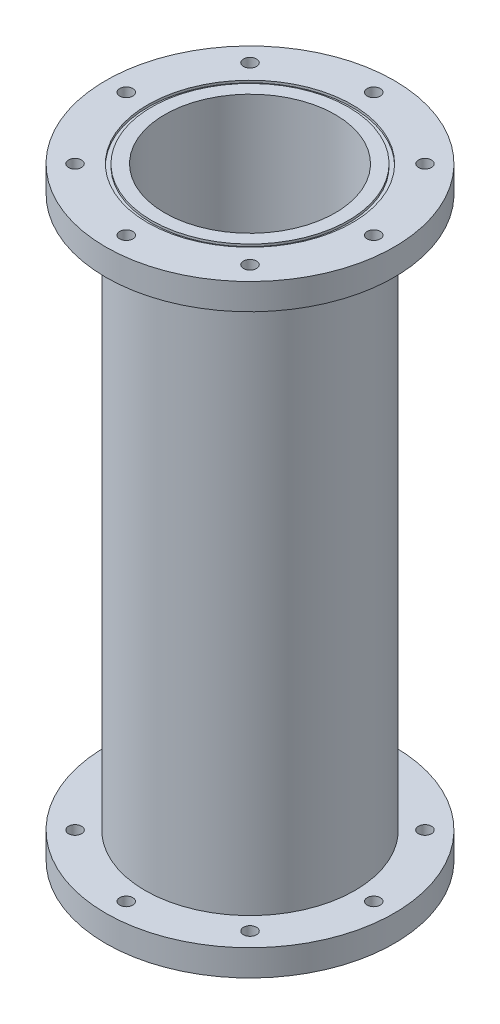
SolidWorks part; units mm, degrees
ref_plane "Front Plane" through (0, 0, 0) normal (0, 0, 1) x (1, 0, 0)
ref_plane "Top Plane" through (0, 0, 0) normal (0, 1, 0) x (1, 0, 0)
ref_plane "Right Plane" through (0, 0, 0) normal (1, 0, 0) x (0, 0, -1)
sketch "Sketch2" plane through (0, 0, 0) normal (0, 1, 0) x (1, 0, 0)
  circle A0 centre (0, 0) radius 41.275
  circle A1 centre (0, 0) radius 50.8
  dimension "D1" = 101.6
  dimension "D2" = 82.55
extrude "Base Cylinder" add sketch "Sketch2" along normal blind 292.1
sketch "Sketch3" plane through (0, 0, 0) normal (0, -1, 0) x (1, 0, 0)
  circle A0 centre (0, 0) radius 41.275
  circle A1 centre (0, 0) radius 69.85
  dimension "D1" = 139.7
extrude "Aft Flange" add sketch "Sketch3" against normal blind 12.7
sketch "Sketch4" plane through (0, 292.1, 0) normal (0, 1, 0) x (1, 0, 0)
  circle A0 centre (0, 0) radius 41.275
  circle A1 centre (0, 0) radius 69.85
extrude "Forward Flange" add sketch "Sketch4" against normal blind 12.7
sketch "Sketch6" plane through (0, 0, 0) normal (0, -1, 0) x (1, 0, 0)
  circle A0 centre (0, 0) radius 49.4792
  circle A1 centre (0, 0) radius 47.625
  dimension "D1" = 98.9584
  dimension "D2" = 95.25
extrude "O-Ring Slot 1" cut sketch "Sketch6" against normal blind 1.1176
sketch "Sketch7" plane through (0, 292.1, 0) normal (0, 1, 0) x (1, 0, 0)
  circle A0 centre (0, 0) radius 49.53
  circle A1 centre (0, 0) radius 47.625
  dimension "D1" = 99.06
  dimension "D2" = 95.25
extrude "O-Ring Slot 2" cut sketch "Sketch7" against normal blind 1.1176
sketch "Sketch8" plane through (0, 0, 0) normal (0, -1, 0) x (1, 0, 0)
  circle A0 centre (-59.9186, 0) radius 3.175
  circle A1 centre (-42.3688, 42.3688) radius 3.175
  circle A2 centre (0, 59.9186) radius 3.175
  circle A3 centre (42.3688, 42.3688) radius 3.175
  circle A4 centre (59.9186, 0) radius 3.175
  circle A5 centre (42.3688, -42.3688) radius 3.175
  circle A6 centre (0, -59.9186) radius 3.175
  circle A7 centre (-42.3688, -42.3688) radius 3.175
  point P36 (0, 0)
  dimension "D2" = 6.35
  dimension "D1" = 59.9186
  dimension "D3" = 8
extrude "Cut-Extrude4" cut sketch "Sketch8" against normal through all both and the other way through all
